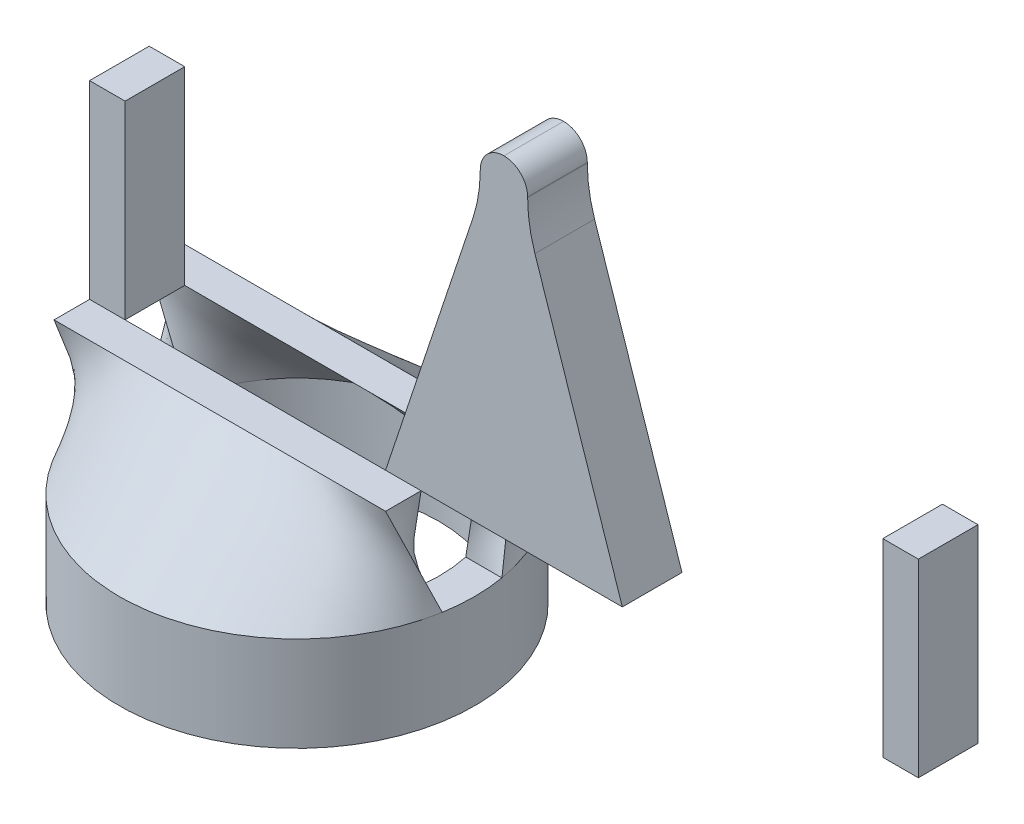
SolidWorks part; units mm, degrees
ref_plane "Front Plane" through (0, 0, 0) normal (0, 0, 1) x (1, 0, 0)
ref_plane "Top Plane" through (0, 0, 0) normal (0, 1, 0) x (1, 0, 0)
ref_plane "Right Plane" through (0, 0, 0) normal (1, 0, 0) x (0, 0, -1)
sketch "Sketch1" plane through (0, 0, 0) normal (0, 0, 1) x (1, 0, 0)
  line L1 (-3.175, 19.05) -> (3.175, 19.05)
  line L2 (3.175, 19.05) -> (3.175, 12.7)
  line L9 (-50.8, -25.4) -> (-50.8, 0)
  line L10 (-50.8, 0) -> (-55.5625, 0)
  line L11 (-55.5625, 0) -> (-55.5625, -25.4)
  line L12 (-55.5625, -25.4) -> (-50.8, -25.4)
  line L13 (-53.1812, 0) -> (0, 19.05) construction
  line L14 (0, 19.05) -> (0, 0) construction
  line L15 (0, 0) -> (-53.1812, 0) construction
  line L16 (55.5625, -25.4) -> (50.8, -25.4)
  line L17 (55.5625, 0) -> (55.5625, -25.4)
  line L18 (50.8, 0) -> (55.5625, 0)
  line L19 (50.8, -25.4) -> (50.8, 0)
  line L20 (-15.875, -25.4) -> (15.875, -25.4)
  line L21 (-3.175, 12.7) -> (-15.875, -25.4)
  line L22 (-3.175, 12.7) -> (-3.175, 19.05)
  line L25 (15.875, -25.4) -> (3.175, 12.7)
  point P4 (0, 19.05)
  dimension "D1" = 6.35
  dimension "D3" = 34.925
  dimension "D5" = 31.75
  dimension "D6" = 4.7625
  dimension "D8" = 19.05
  dimension "D10" = 6.35
  dimension "D11" = 25.4
extrude "Boss-Extrude1" add sketch "Sketch1" along normal mid plane 8
fillet "Fillet1" radius 3.175 2 edges at (3.175, 19.05, 0) (-3.175, 19.05, 0)
fillet "Fillet4" radius 19.05 2 edges at (3.175, 12.7, 0) (-3.175, 12.7, 0)
sketch "Sketch2" plane through (0, 0, -4) normal (0, 0, 1) x (1, 0, 0)
  line L0 (0, 19.05) -> (0, -25.4) construction
  line L2 (-15.875, -25.4) -> (15.875, -25.4) construction
ref_plane "Plane1" through (0, -38.1, 0) normal (0, -1, 0) x (-1, 0, 0)
sketch "Sketch4" plane through (0, -38.1, 0) normal (0, -1, 0) x (-1, 0, 0)
  line L0 (50.8, -4) -> (50.8, 4) construction
  line L2 (8.2759, 4) -> (13.1247, 4)
  line L5 (55.2241, 4) -> (50.3753, 4)
  line L7 (55.5625, 4) -> (50.8, 4) construction
  line L8 (15.875, 4) -> (-15.875, 4) construction
  arc A2 (50.3753, 4) -> (13.1247, 4) centre (31.75, 0) ccw
  arc A3 (55.2241, 4) -> (8.2759, 4) centre (31.75, 0) ccw
  circle A4 centre (31.75, 0) radius 23.8125 construction
  circle A5 centre (31.75, 0) radius 19.05 construction
  point P0 (12.8443, 2.3403)
  point P1 (44.45, 0)
  point P7 (47.625, 0)
  point P10 (26.9875, 0)
  point P11 (6.35, 0)
  dimension "D2" = 19.05
  dimension "D1" = 4.7625
sketch "Sketch13" plane through (0, -25.4, 0) normal (0, -1, 0) x (1, 0, 0)
  line L0 (-55.2241, -4) -> (-50.3753, -4) construction
  line L1 (-55.5625, -4) -> (-11.1125, -4)
  line L2 (-55.5625, -4) -> (-55.5625, -8.7625)
  line L3 (-55.5625, -8.7625) -> (-11.1125, -8.7625)
  line L4 (-11.1125, -4) -> (-11.1125, -8.7625)
  line L5 (-15.875, 4) -> (-15.875, -4) construction
  line L6 (-50.8, 4) -> (-50.8, -4) construction
  dimension "D1" = 4.7625
  dimension "D2" = 4.7625
  dimension "D3" = 4.7625
loft "Loft6" add profiles "Sketch13", "Sketch4" connector at (-55.5625, -25.4, -4) connector at (-50.3753, -38.1, -4)
sketch "Sketch14" plane through (0, -25.4, 0) normal (0, 1, 0) x (1, 0, 0)
  line L1 (-55.5625, 8.7625) -> (-11.1125, 8.7625)
  line L2 (-55.5625, 8.7625) -> (-55.5625, 4)
  line L3 (-55.5625, 4) -> (-11.1125, 4)
  line L4 (-11.1125, 8.7625) -> (-11.1125, 4)
sketch "Sketch15" plane through (0, -25.4, 0) normal (0, -1, 0) x (-1, 0, 0)
  line L1 (55.5625, -4) -> (11.1125, -4)
  line L2 (55.5625, -4) -> (55.5625, -8.7625)
  line L3 (55.5625, -8.7625) -> (11.1125, -8.7625)
  line L4 (11.1125, -4) -> (11.1125, -8.7625)
  line L5 (15.875, -4) -> (15.875, 4) construction
  dimension "D1" = 4.7625
  dimension "D2" = 4.7625
sketch "Sketch16" plane through (0, -38.1, 0) normal (0, -1, 0) x (-1, 0, 0)
  line L0 (55.2241, -4) -> (50.3753, -4)
  line L1 (55.5625, -4) -> (11.1125, -4) construction
  line L2 (13.1247, -4) -> (8.2759, -4)
  arc A0 (13.1247, -4) -> (50.3753, -4) centre (31.75, 0) ccw
  arc A1 (8.2759, -4) -> (55.2241, -4) centre (31.75, 0) ccw
  arc A2 (50.3753, 4) -> (13.1247, 4) centre (31.75, 0) ccw construction
  circle A3 centre (31.75, 0) radius 19.05 construction
  circle A4 centre (31.75, 0) radius 23.8125 construction
  dimension "D1" = 4.7625
loft "Loft7" add profiles "Sketch16", "Sketch15" connector at (-55.2241, -38.1, 4) connector at (-55.5625, -25.4, 8.7625)
sketch "Sketch17" plane through (0, -38.1, 0) normal (0, -1, 0) x (-1, 0, 0)
  circle A0 centre (31.75, 0) radius 19.05
  arc A2 (13.1247, -4) -> (50.3753, -4) centre (31.75, 0) ccw construction
  circle A3 centre (31.75, 0) radius 23.8125
  dimension "D1" = 4.7625
extrude "Boss-Extrude2" add sketch "Sketch17" along normal blind 12.7
